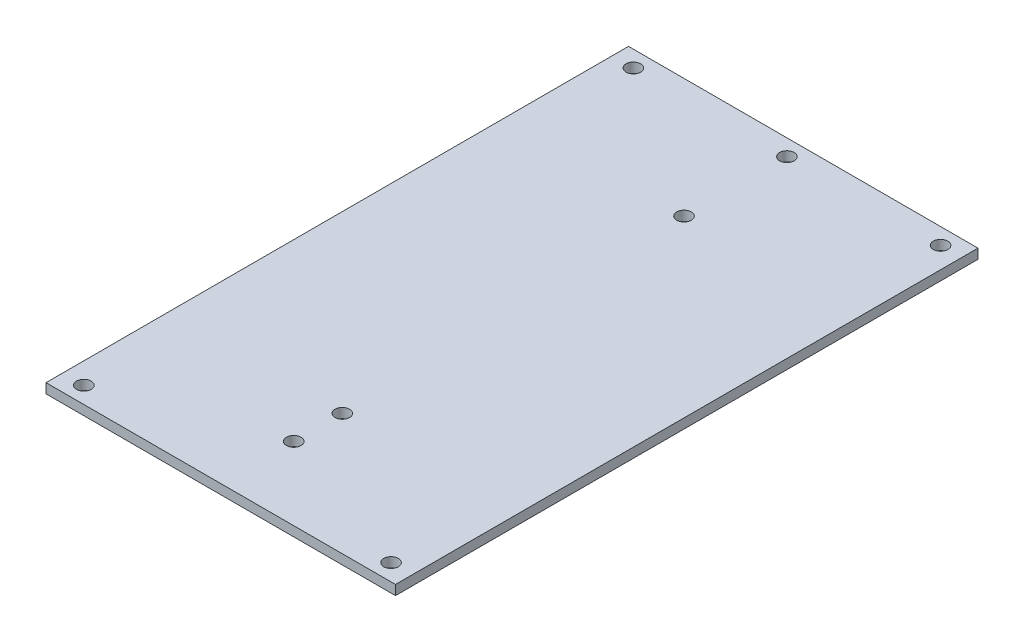
SolidWorks part; units mm, degrees
ref_plane "Front Plane" through (0, 0, 0) normal (0, 0, 1) x (1, 0, 0)
ref_plane "Top Plane" through (0, 0, 0) normal (0, 1, 0) x (1, 0, 0)
ref_plane "Right Plane" through (0, 0, 0) normal (1, 0, 0) x (0, 0, -1)
sketch "Sketch1" plane through (0, 0, 0) normal (0, 1, 0) x (1, 0, 0)
  line L0 (0, -146.05) -> (0, 146.05) construction
  line L5 (-100.457, 213.36) -> (100.457, 213.36)
  line L6 (0, 213.36) -> (0, -109.22) construction
  line L7 (-100.457, -146.05) -> (100.457, -146.05)
  line L8 (0, -146.05) -> (0, 213.36) construction
  line L9 (-114.3, 224.028) -> (114.3, 224.028)
  line L10 (114.3, 224.028) -> (114.3, -156.972)
  line L11 (114.3, -156.972) -> (-114.3, -156.972)
  line L12 (-114.3, -156.972) -> (-114.3, 224.028)
  circle A0 centre (0, 146.05) radius 4.7625
  circle A1 centre (-100.457, -146.05) radius 4.7625
  circle A2 centre (100.457, -146.05) radius 4.7625
  circle A3 centre (0, 213.36) radius 4.7625
  circle A4 centre (0, -109.22) radius 4.7625
  circle A5 centre (-100.457, 213.36) radius 4.7625
  circle A6 centre (100.457, 213.36) radius 4.7625
  circle A7 centre (0, -77.47) radius 4.7625
  point P0 (0, 0)
  point P8 (0, 0)
  point P13 (0, -146.05)
  point P19 (0, 213.36)
  point P27 (0, -156.972)
  dimension "D4" = 9.525
  dimension "D1" = 359.41
  dimension "D2" = 322.58
  dimension "D3" = 292.1
  dimension "D5" = 200.914
  dimension "D6" = 290.83
  dimension "D7" = 228.6
  dimension "D8" = 381
  dimension "D9" = 10.922
extrude "Boss-Extrude1" add sketch "Sketch1" along normal blind 6.35 contours L12 L11 L10 L9 A7 A6 A3 A5 A4 A2 A1 A0 region at (0, 0, -33.4958)
